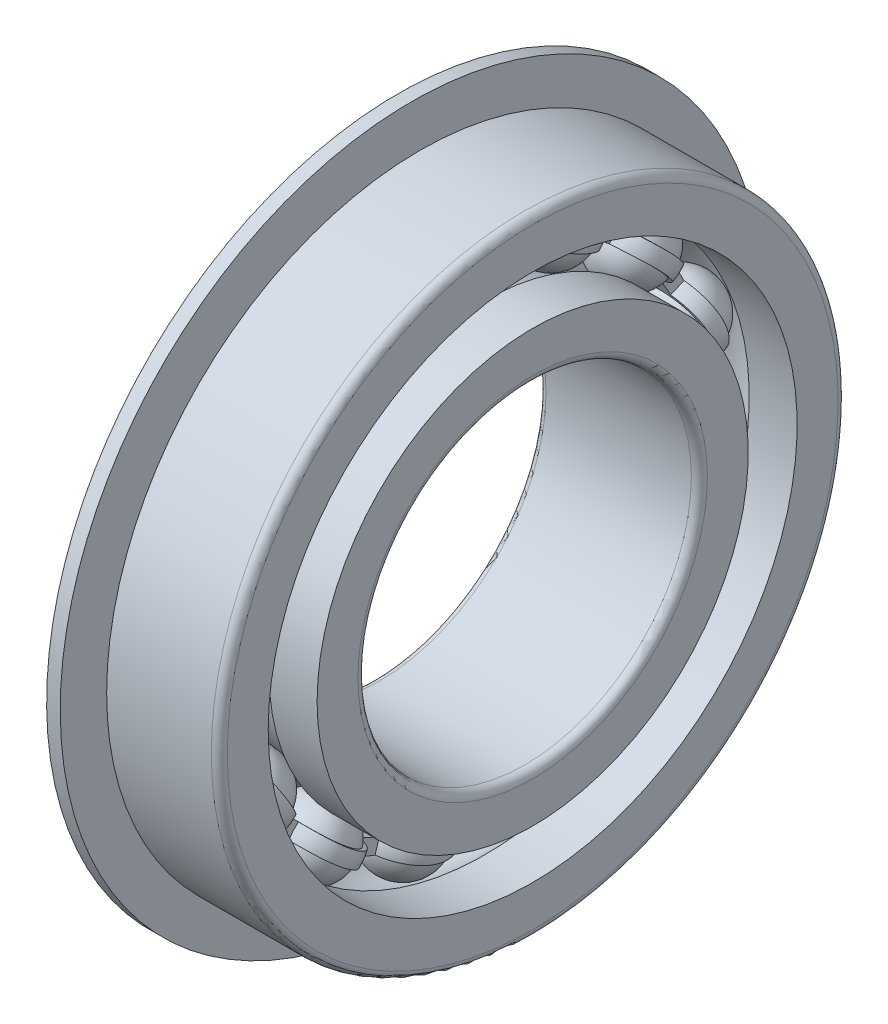
SolidWorks part; units mm, degrees
material "AISI 304"
ref_plane "前视基准面" through (0, 0, 0) normal (0, 0, 1) x (1, 0, 0)
ref_plane "上视基准面" through (0, 0, 0) normal (0, 1, 0) x (1, 0, 0)
ref_plane "右视基准面" through (0, 0, 0) normal (1, 0, 0) x (0, 0, -1)
sketch "尺寸草图" plane through (0, 0, 0) normal (0, 0, 1) x (1, 0, 0)
  line L0 (-19.9271, 0) -> (19.9271, 0) construction
  line L1 (0, 21.603) -> (0, -21.603) construction
  line L2 (-5.5, 23.5) -> (5.4, 23.5)
  line L3 (6, 22.9) -> (6, 20.3333)
  line L4 (-6, 23) -> (-6, 20.3333)
  line L5 (-5.5, 19.8333) -> (5.5, 19.8333)
  line L6 (-3.5, 18) -> (3.3577, 18) construction
  line L7 (-5.5, 16.1667) -> (5.5, 16.1667)
  line L8 (6, 15.6667) -> (6, 13.1)
  line L9 (5.4, 12.5) -> (-5.5, 12.5)
  line L10 (-6, 13) -> (-6, 15.6667)
  line L11 (0, 18) -> (0, 20.75) construction
  line L12 (-4.1, 23.5) -> (-4.1, 22.175)
  line L13 (-4.1, 22.175) -> (-2.45, 22.175)
  line L14 (-2.45, 22.175) -> (-2.45, 23.5)
  line L15 (-4.1, 23.5) -> (-4.1, 26.35)
  line L16 (-4.1, 26.35) -> (-3.08, 26.35)
  line L17 (-3.08, 26.35) -> (-3.08, 22.175)
  line L18 (-2, 0) -> (2, 0) construction
  circle A0 centre (0, 18) radius 2.75
  arc A1 (6, 20.3333) -> (5.5, 19.8333) centre (5.5, 20.3333) cw
  arc A2 (6, 15.6667) -> (5.5, 16.1667) centre (5.5, 15.6667) ccw
  arc A3 (-5.5, 16.1667) -> (-6, 15.6667) centre (-5.5, 15.6667) ccw
  arc A4 (-5.5, 19.8333) -> (-6, 20.3333) centre (-5.5, 20.3333) cw
  arc A5 (-5.5, 12.5) -> (-6, 13) centre (-5.5, 13) cw
  arc A6 (5.4, 12.5) -> (6, 13.1) centre (5.4, 13.1) ccw
  arc A7 (6, 22.9) -> (5.4, 23.5) centre (5.4, 22.9) ccw
  arc A8 (-5.5, 23.5) -> (-6, 23) centre (-5.5, 23) ccw
  arc A9 (-2.45, 22.575) -> (-2.85, 22.175) centre (-2.85, 22.575) cw
  point P7 (0, 0)
  point P25 (-6, 16.1667)
  point P28 (-6, 19.8333)
  point P31 (-6, 12.5)
  point P36 (6, 23.5)
  point P39 (-6, 23.5)
  dimension "D1" = 0.9167
  dimension "r1" = 0.5
  dimension "r0-" = 0.4
  dimension "r" = 0.6
  dimension "B" = 12
  dimension "D2" = 6
  dimension "D" = 47
  dimension "(d)" = 25
  dimension "D5" = 18
  dimension "D6" = 3.6667
  dimension "D7" = 3.6667
  dimension "a-" = 1.9
  dimension "D2-" = 52.7
  dimension "D1-" = 44.35
  dimension "b-" = 1.65
  dimension "f-" = 1.02
  dimension "g" = 4
sketch "草图2" plane through (0, 0, 0) normal (0, 0, 1) x (1, 0, 0)
  line L0 (-6, 20.3333) -> (-6, 19.8333)
  line L1 (-6, 19.8333) -> (-5.5, 19.8333)
  line L2 (5.5, 19.8333) -> (6, 19.8333)
  line L3 (6, 19.8333) -> (6, 20.3333)
  line L4 (-5.5, 16.1667) -> (-6, 16.1667)
  line L5 (-6, 16.1667) -> (-6, 15.6667)
  line L6 (5.4, 12.5) -> (-5.5, 12.5) construction
  line L7 (5.5, 16.1667) -> (6, 16.1667)
  line L8 (-6, 23) -> (-6, 20.3333) construction
  line L9 (-5.5, 19.8333) -> (5.5, 19.8333) construction
  line L10 (-5.5, 23.5) -> (5.4, 23.5) construction
  line L11 (6, 22.9) -> (6, 20.3333) construction
  line L12 (6, 15.6667) -> (6, 13.1) construction
  line L13 (-5.5, 16.1667) -> (5.5, 16.1667) construction
  line L14 (5.4, 12.5) -> (-5.5, 12.5)
  line L15 (-6, 13) -> (-6, 15.6667) construction
  line L16 (6, 16.1667) -> (6, 15.6667)
  line L18 (-3.5, 0) -> (3.5, 0) construction
  line L19 (-19.9271, 0) -> (19.9271, 0) construction
  line L20 (-6, 23) -> (-6, 20.3333)
  line L21 (-5.5, 19.8333) -> (-2.0497, 19.8333)
  line L22 (-5.5, 23.5) -> (5.4, 23.5)
  line L23 (6, 22.9) -> (6, 20.3333)
  line L24 (6, 15.6667) -> (6, 13.1)
  line L25 (-5.5, 16.1667) -> (-2.0497, 16.1667)
  line L26 (-6, 13) -> (-6, 15.6667)
  line L27 (2.0497, 19.8333) -> (5.5, 19.8333)
  line L28 (2.0497, 16.1667) -> (5.5, 16.1667)
  circle A0 centre (0, 18) radius 2.75 construction
  arc A1 (2.0497, 19.8333) -> (-2.0497, 19.8333) centre (0, 18) ccw
  arc A2 (-2.0497, 16.1667) -> (2.0497, 16.1667) centre (0, 18) ccw
  arc A3 (-5.5, 23.5) -> (-6, 23) centre (-5.5, 23) ccw construction
  arc A4 (-6, 20.3333) -> (-5.5, 19.8333) centre (-5.5, 20.3333) ccw construction
  arc A5 (6, 22.9) -> (5.4, 23.5) centre (5.4, 22.9) ccw construction
  arc A6 (5.5, 19.8333) -> (6, 20.3333) centre (5.5, 20.3333) ccw construction
  arc A7 (6, 15.6667) -> (5.5, 16.1667) centre (5.5, 15.6667) ccw construction
  arc A8 (5.4, 12.5) -> (6, 13.1) centre (5.4, 13.1) ccw construction
  arc A9 (-5.5, 16.1667) -> (-6, 15.6667) centre (-5.5, 15.6667) ccw construction
  arc A10 (-6, 13) -> (-5.5, 12.5) centre (-5.5, 13) ccw construction
  arc A11 (-5.5, 23.5) -> (-6, 23) centre (-5.5, 23) ccw
  arc A12 (-6, 20.3333) -> (-5.5, 19.8333) centre (-5.5, 20.3333) ccw construction
  arc A13 (6, 22.9) -> (5.4, 23.5) centre (5.4, 22.9) ccw
  arc A14 (5.5, 19.8333) -> (6, 20.3333) centre (5.5, 20.3333) ccw construction
  arc A15 (6, 15.6667) -> (5.5, 16.1667) centre (5.5, 15.6667) ccw construction
  arc A16 (5.4, 12.5) -> (6, 13.1) centre (5.4, 13.1) ccw
  arc A17 (-5.5, 16.1667) -> (-6, 15.6667) centre (-5.5, 15.6667) ccw construction
  arc A18 (-6, 13) -> (-5.5, 12.5) centre (-5.5, 13) ccw
revolve "旋转1" add sketch "草图2" angle 360 about L18 region at (-0.0033, 21.7534, 0) region at (-0.0033, 14.2466, 0)
sketch "草图5" plane through (0, 0, 0) normal (0, 0, 1) x (1, 0, 0)
  line L1 (-0.825, 17.45) -> (0.825, 17.45)
  line L2 (-0.825, 17.45) -> (-0.825, 18.55)
  line L3 (-0.825, 18.55) -> (0.825, 18.55)
  line L4 (0.825, 17.45) -> (0.825, 18.55)
  line L5 (-0.825, 17.45) -> (0.825, 18.55) construction
  line L6 (-0.825, 18.55) -> (0.825, 17.45) construction
  circle A0 centre (0, 18) radius 2.75 construction
  circle A1 centre (0, 18) radius 2.75 construction
  point P0 (0, 18)
  dimension "D1" = 1.65
  dimension "D2" = 1.1
revolve "旋转3" add sketch "草图5" angle 360 about L0
sketch "草图3" plane through (0, 0, 0) normal (0, 0, 1) x (1, 0, 0)
  line L1 (-3.025, 18) -> (3.025, 18)
  circle A0 centre (0, 18) radius 2.75 construction
  circle A1 centre (0, 18) radius 2.75 construction
  arc A2 (3.025, 18) -> (-3.025, 18) centre (0, 18) ccw
  dimension "D2" = 6.05
revolve "旋转2" add sketch "草图3" angle 360 about L1 region at (0, 19.2838, 0)
ref_axis "基准轴1" through (-3.85, 0, 0) along (1, 0, 0)
pattern_circular "阵列(圆周)5" count 15 over 360 about axis through (-3.85, 0, 0) along (1, 0, 0) of bodies 103
sketch "草图6" plane through (0, 0, 0) normal (0, 0, 1) x (1, 0, 0)
  line L0 (-2.9746, 18.55) -> (2.9746, 18.55)
  line L1 (-3.5, 18) -> (6, 18) construction
  line L3 (-2.9746, 17.45) -> (2.9746, 17.45)
  line L4 (6, -22.9) -> (6, 22.9) construction
  arc A0 (-2.9746, 17.45) -> (2.9746, 17.45) centre (0, 18) ccw
  circle A1 centre (0, 18) radius 2.75 construction
  circle A2 centre (0, 18) radius 2.75 construction
  arc A3 (2.9746, 18.55) -> (-2.9746, 18.55) centre (0, 18) ccw
  dimension "D1" = 6.05
  dimension "D3" = 0.55
  dimension "D4" = 0.55
revolve "切除-旋转1" cut sketch "草图6" angle 360 about L0
sketch "草图7" plane through (0, 0, 0) normal (0, 0, 1) x (1, 0, 0)
  line L0 (-2.75, 18) -> (2.75, 18)
  line L1 (-6, 0) -> (6, 0) construction
  line L2 (-6, 23) -> (-6, -23) construction
  line L3 (6, -22.9) -> (6, 22.9) construction
  circle A0 centre (0, 18) radius 2.75 construction
  arc A1 (2.75, 18) -> (-2.75, 18) centre (0, 18) ccw
revolve "旋转4" add sketch "草图7" angle 360 about L0
pattern_circular "阵列(圆周)2" count 15 over 360 about axis through (-3.85, 0, 0) along (1, 0, 0) of "旋转4"
sketch "草图8" plane through (0, 0, 0) normal (0, 0, 1) x (1, 0, 0)
  line L0 (-4.1, 22.175) -> (-2.45, 22.175) construction
  line L2 (-4.1, 22.175) -> (-2.45, 22.175)
  line L3 (-2.45, 22.175) -> (-2.45, 23.5)
  line L4 (-4.1, 22.175) -> (-4.1, 23.5)
  line L5 (-4.1, 23.5) -> (-2.45, 23.5)
  line L6 (-2.45, 22.175) -> (-2.45, 23.5) construction
revolve "切除-旋转2" cut sketch "草图8" angle 360 about L0
sketch "草图9" plane through (0, 0, 0) normal (0, 0, 1) x (1, 0, 0)
  line L0 (-4.1, 26.35) -> (-3.08, 26.35) construction
  line L1 (-3.08, 26.35) -> (-3.08, 22.175) construction
  line L2 (-4.1, 23.5) -> (-4.1, 26.35) construction
  line L3 (-4.1, 23.5) -> (-4.1, 22.175) construction
  line L4 (-4.1, 22.175) -> (-2.45, 22.175) construction
  line L5 (-4.1, 26.35) -> (-3.08, 26.35)
  line L6 (-3.08, 26.35) -> (-3.08, 22.175)
  line L7 (-4.1, 23.5) -> (-4.1, 26.35)
  line L8 (-4.1, 23.5) -> (-4.1, 22.175)
  line L9 (-4.1, 22.175) -> (-3.08, 22.175)
revolve "旋转5" add sketch "草图9" angle 360 about L0
sketch "草图11" plane through (0, 0, 0) normal (1, 0, 0) x (0, 0, -1)
  line L0 (0, 21.603) -> (0, -21.603) construction
  line L2 (-2, -22.0846) -> (-2, -31.62)
  line L3 (-2, -31.62) -> (2, -31.62)
  line L4 (2, -22.0846) -> (2, -31.62)
  arc A0 (-2, -22.0846) -> (2, -22.0846) centre (0, 0) ccw
  point P7 (0, -31.62)
  dimension "D1" = 4
  dimension "D2" = 31.62
extrude "切除-拉伸1" cut sketch "草图11" against normal up to vertex from vertex up to point (-4.1, 26.35, 0) starting at point (-3.08, 26.35, 0)
fillet "圆角1" radius 0.4 2 edges at (-2.45, 0, 22.175) (-4.1, -22.175, 0)
